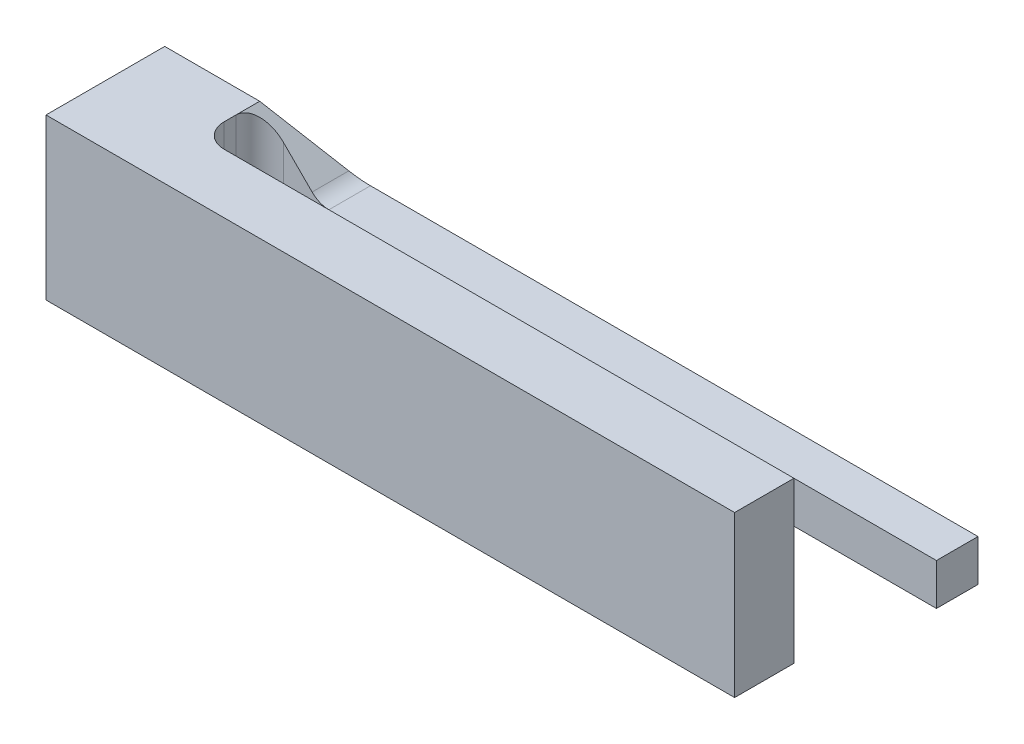
SolidWorks part; units mm, degrees
ref_plane "前视基准面" through (0, 0, 0) normal (0, 0, 1) x (1, 0, 0)
ref_plane "上视基准面" through (0, 0, 0) normal (0, 1, 0) x (1, 0, 0)
ref_plane "右视基准面" through (0, 0, 0) normal (1, 0, 0) x (0, 0, -1)
other "Configuration Table"
sketch "草图1" plane through (0, 0, 0) normal (0, 0, 1) x (1, 0, 0)
  line L1 (-14.5662, 13.249) -> (45.4338, 13.249)
  line L2 (-14.5662, 13.249) -> (-14.5662, 9.749)
  line L3 (-14.5662, 9.749) -> (45.4338, 9.749)
  line L4 (45.4338, 13.249) -> (45.4338, 9.749)
  line L5 (-14.5662, 13.249) -> (45.4338, 9.749) construction
  line L6 (-14.5662, 9.749) -> (45.4338, 13.249) construction
  point P0 (15.4338, 11.499)
extrude "凸台-拉伸1" add sketch "草图1" along normal blind 3.5
sketch "草图2" plane through (0, 0, 3.5) normal (0, 0, 1) x (1, 0, 0)
  line L0 (-14.5662, 9.749) -> (-14.5662, 4.749)
  line L1 (-14.5662, 13.249) -> (-14.5662, 18.249)
  line L3 (-14.5662, 18.249) -> (-11.5662, 18.249)
  line L4 (-14.5662, 18.249) -> (-14.5662, 4.749)
  line L5 (-14.5662, 4.749) -> (-11.5662, 4.749)
  line L6 (-11.5662, 18.249) -> (-11.5662, 4.749)
  line M4 (45.4338, 13.249) -> (-14.5662, 13.249)
  line M5 (-14.5662, 13.249) -> (-14.5662, 9.749)
  line M6 (-14.5662, 9.749) -> (45.4338, 9.749)
extrude "凸台-拉伸2" add sketch "草图2" along normal blind 10 contours L6 L3 L1 M4 | L6 M4 M5 M6 | L6 L0 L5 M6 region at (-13.0662, 7.249, 3.5) region at (-13.0662, 11.499, 3.5) region at (-13.0662, 15.749, 3.5)
sketch "草图3" plane through (-14.5662, 0, 0) normal (-1, 0, 0) x (0, 0, 1)
  line L0 (3.5, 18.249) -> (0, 13.249)
  line L1 (0, 13.249) -> (0, 9.749)
  line L2 (0, 9.749) -> (3.5, 4.749)
  line L11 (0, 13.249) -> (0, 9.749)
  line L12 (0, 9.749) -> (3.5, 9.749)
  line L13 (3.5, 9.749) -> (3.5, 4.749)
  line L14 (3.5, 4.749) -> (13.5, 4.749)
  line L15 (13.5, 4.749) -> (13.5, 18.249)
  line L16 (13.5, 18.249) -> (3.5, 18.249)
  line L17 (3.5, 18.249) -> (3.5, 13.249)
  line L18 (3.5, 13.249) -> (0, 13.249)
  line L19 (0, 13.249) -> (0, 9.749)
  line L20 (0, 9.749) -> (3.5, 9.749)
  line L21 (3.5, 9.749) -> (3.5, 4.749)
  line L25 (3.5, 18.249) -> (3.5, 13.249)
  line L26 (3.5, 13.249) -> (0, 13.249)
  line M10 (0, 9.749) -> (3.5, 9.749)
  line M11 (3.5, 9.749) -> (3.5, 4.749)
  line M15 (3.5, 18.249) -> (3.5, 13.249)
  line M16 (3.5, 13.249) -> (0, 13.249)
  dimension "D1" = 0
extrude "凸台-拉伸3" add sketch "草图3" against normal blind 3 contours L2 M10 M11 | L0 M15 M16 region at (-14.5662, 14.9157, 2.3333) region at (-14.5662, 8.0824, 2.3333)
sketch "草图4" plane through (-11.5662, 0, 0) normal (1, 0, 0) x (0, 0, -1)
  line L0 (-13.5, 8.749) -> (-13.5, 14.249)
  line L1 (-13.5, 18.249) -> (-8.5, 18.249)
  line L2 (-13.5, 18.249) -> (-13.5, 14.249)
  line L3 (-13.5, 14.249) -> (-8.5, 14.249)
  line L4 (-8.5, 18.249) -> (-8.5, 14.249)
  line L5 (-13.5, 4.749) -> (-8.5, 4.749)
  line L6 (-13.5, 4.749) -> (-13.5, 8.749)
  line L7 (-13.5, 8.749) -> (-8.5, 8.749)
  line L8 (-8.5, 4.749) -> (-8.5, 8.749)
  line L9 (-8.5, 8.749) -> (-8.5, 14.249)
  line M12 (-3.5, 18.249) -> (-13.5, 18.249)
  line M13 (-13.5, 18.249) -> (-13.5, 4.749)
  line M14 (-13.5, 4.749) -> (-3.5, 4.749)
extrude "凸台-拉伸4" add sketch "草图4" along normal blind 50 contours L7 L9 L3 M13 | L8 L7 M14 M13 | L4 L3 M12 M13 region at (-11.5662, 6.749, 11) region at (-11.5662, 11.499, 11) region at (-11.5662, 16.249, 11)
chamfer "倒角1" distance 5 angle 45 2 edges at (-11.5662, 9.749, 1.75) (-11.5662, 13.249, 1.75)
fillet "圆角1" radius 2 4 edges at (-11.5662, 11.499, 8.5) (-6.5662, 13.249, 1.75) (-6.5662, 9.749, 1.75) (-11.5662, 11.499, 3.5)
ref_plane "基准面1" through (-14.5662, 0, 0) normal (-1, 0, 0) x (0, 0, 1)
sketch "草图5" plane through (-14.5662, 0, 0) normal (-1, 0, 0) x (0, 0, 1)
  line L6 (3.5, 18.249) -> (0, 13.249)
  line L7 (0, 13.249) -> (0, 9.749)
  line L8 (0, 9.749) -> (3.5, 4.749)
  line L9 (3.5, 4.749) -> (13.5, 4.749)
  line L10 (13.5, 4.749) -> (13.5, 18.249)
  line L11 (13.5, 18.249) -> (3.5, 18.249)
  line L12 (3.5, 18.249) -> (0, 13.249)
  line L13 (0, 13.249) -> (0, 9.749)
  line L14 (0, 9.749) -> (3.5, 4.749)
  line L15 (3.5, 4.749) -> (13.5, 4.749)
  line L16 (13.5, 4.749) -> (13.5, 18.249)
  line L17 (13.5, 18.249) -> (3.5, 18.249)
  dimension "D1" = 0
extrude "凸台-拉伸5" add sketch "草图5" along normal blind 5
